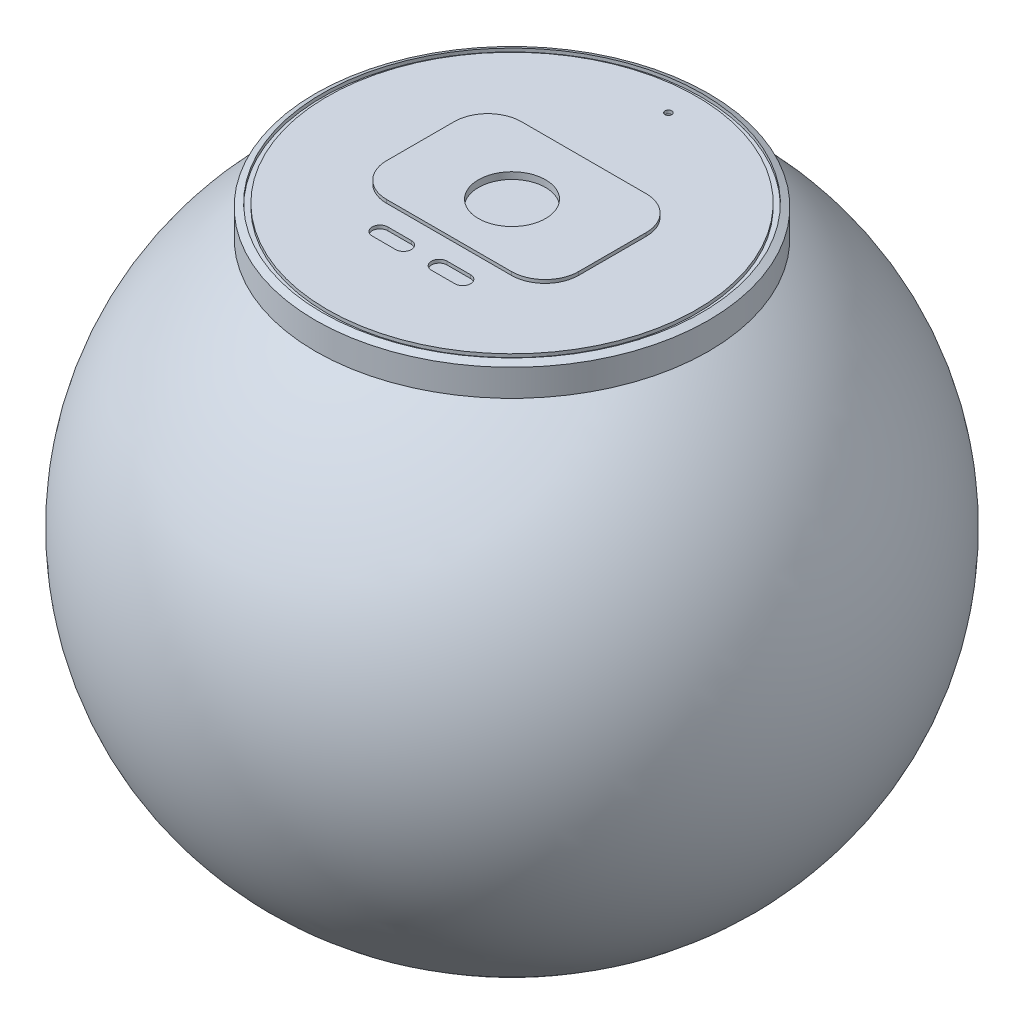
SolidWorks part; units mm, degrees
ref_plane "Front Plane" through (0, 0, 0) normal (0, 0, 1) x (1, 0, 0)
ref_plane "Top Plane" through (0, 0, 0) normal (0, 1, 0) x (1, 0, 0)
ref_plane "Right Plane" through (0, 0, 0) normal (1, 0, 0) x (0, 0, -1)
sketch "Sketch1" plane through (0, 0, 0) normal (0, 0, 1) x (1, 0, 0)
  line L0 (0, 0) -> (0, 49.509) construction
  line L1 (0, 49.509) -> (0, -35)
  line L2 (0, -35) -> (-25.272, -35)
  arc A0 (0, 49.509) -> (-25.272, -35) centre (-4.0728, 4.6937) ccw
  dimension "D2" = 45
  dimension "D1" = 35
revolve "Revolve1" add sketch "Sketch1" angle 360 about L0
sketch "Sketch2" plane through (0, 0, 0) normal (0, 0, 1) x (1, 0, 0)
  line L0 (0, 0) -> (0, 66.1042) construction
  line L2 (57.5278, 42) -> (57.5278, 50)
  line L3 (57.5278, 50) -> (-10, 50)
  line L4 (-10, 50) -> (-49.6146, 50)
  line L5 (-49.6146, 50) -> (-49.6146, 42)
  line L6 (-49.6146, 42) -> (57.5278, 42)
  dimension "D1" = 68
  dimension "D2" = 50
  dimension "D3" = 10
  dimension "D4" = 8
extrude "Cut-Extrude1" cut sketch "Sketch2" against normal through all both and the other way through all contours L3 L4 L5 L6 L2
sketch "Sketch8" plane through (0, 0, 0) normal (0, 0, 1) x (1, 0, 0)
  line L0 (-29.2371, 42) -> (-29.2371, 46)
  line L2 (-29.2371, 42) -> (-28.2371, 42)
  line L3 (29.2371, 42) -> (-29.2371, 42) construction
  line L4 (-28.2371, 42) -> (-28.2371, 46.5)
  line L5 (-28.2371, 46.5) -> (-29.2371, 46)
  line L6 (0, 0) -> (0, 76.8705) construction
revolve "Revolve2" add sketch "Sketch8" angle 360 about L6
sketch "Sketch9" plane through (0, 42, 0) normal (0, 1, 0) x (1, 0, 0)
  circle A0 centre (0, 0) radius 28.2371
extrude "Boss-Extrude3" add sketch "Sketch9" along normal blind 4.5
sketch "Sketch10" plane through (0, 46.5, 0) normal (0, 1, 0) x (1, 0, 0)
  circle A0 centre (0, 0) radius 27.476
  circle A1 centre (0, 0) radius 28.2371
extrude "Cut-Extrude2" cut sketch "Sketch10" against normal blind 0.5
sketch "Sketch11" plane through (0, 46.5, 0) normal (0, 1, 0) x (1, 0, 0)
  line L0 (0, -61.2711) -> (0, 61.2711)
  line L1 (9.2848, 10.6836) -> (-9.2848, 10.6836)
  line L2 (-14.2848, 5.6836) -> (-14.2848, -4.3676)
  line L3 (-9.2848, -9.3676) -> (9.2848, -9.3676)
  line L4 (14.2848, 5.6836) -> (14.2848, -4.3676)
  line L5 (-2.6624, -12.3155) -> (-6.1588, -12.3155)
  line L6 (-6.1588, -14.6519) -> (-2.6624, -14.6519)
  line L7 (2.6624, -12.3155) -> (6.1588, -12.3155)
  line L8 (6.1588, -14.6519) -> (2.6624, -14.6519)
  circle A0 centre (0, 0) radius 5
  arc A1 (-6.1588, -12.3155) -> (-6.1588, -14.6519) centre (-6.1588, -13.4837) ccw
  arc A2 (-2.6624, -12.3155) -> (-2.6624, -14.6519) centre (-2.6624, -13.4837) cw
  arc A3 (6.1588, -12.3155) -> (6.1588, -14.6519) centre (6.1588, -13.4837) cw
  arc A4 (2.6624, -12.3155) -> (2.6624, -14.6519) centre (2.6624, -13.4837) ccw
  circle A5 centre (0, 23.2655) radius 0.5
  arc A6 (-14.2848, -4.3676) -> (-9.2848, -9.3676) centre (-9.2848, -4.3676) ccw
  arc A7 (14.2848, -4.3676) -> (9.2848, -9.3676) centre (9.2848, -4.3676) cw
  arc A8 (14.2848, 5.6836) -> (9.2848, 10.6836) centre (9.2848, 5.6836) ccw
  arc A9 (-9.2848, 10.6836) -> (-14.2848, 5.6836) centre (-9.2848, 5.6836) ccw
  point P6 (0, 0)
  point P11 (0, -9.3676)
  point P12 (0, 10.6836)
  point P29 (-14.2848, -9.3676)
  point P32 (14.2848, -9.3676)
  point P35 (14.2848, 10.6836)
  point P38 (-14.2848, 10.6836)
  dimension "D1" = 5
extrude "Cut-Extrude4" cut sketch "Sketch11" against normal blind 0.5 contours L6 A2 L5 A1
extrude "Cut-Extrude5" cut sketch "Sketch11<7>" against normal blind 0.5 contours L7 A3 L8 A4
sketch "Sketch11<7>" plane through (0, 46.5, 0) normal (0, 1, 0) x (1, 0, 0) same geometry as "Sketch11"
extrude "Boss-Extrude5" add sketch "Sketch11<10>" along normal blind 0.5 contours L4 A7 L3 A6 L2 A9 L1 A8
sketch "Sketch11<10>" plane through (0, 46.5, 0) normal (0, 1, 0) x (1, 0, 0) same geometry as "Sketch11"
extrude "Cut-Extrude7" cut sketch "Sketch11<11>" against normal blind 0.5 and the other way blind 0.5 contours A0
sketch "Sketch11<11>" plane through (0, 46.5, 0) normal (0, 1, 0) x (1, 0, 0) same geometry as "Sketch11"
extrude "Cut-Extrude8" cut sketch "Sketch11<12>" against normal blind 0.5 contours A5
sketch "Sketch11<12>" plane through (0, 46.5, 0) normal (0, 1, 0) x (1, 0, 0) same geometry as "Sketch11"
